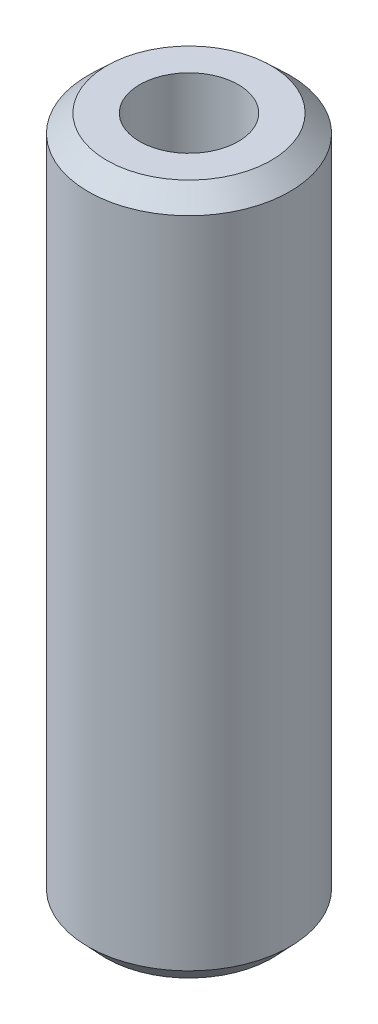
SolidWorks part; units mm, degrees
ref_plane "Front Plane" through (0, 0, 0) normal (0, 0, 1) x (1, 0, 0)
ref_plane "Top Plane" through (0, 0, 0) normal (0, 1, 0) x (1, 0, 0)
ref_plane "Right Plane" through (0, 0, 0) normal (1, 0, 0) x (0, 0, -1)
sketch "Sketch1" plane through (0, 0, 0) normal (0, 1, 0) x (1, 0, 0)
  circle A0 centre (0, 0) radius 15
  dimension "SHAFT_OD" = 30
extrude "Boss-Extrude1" add sketch "Sketch1" along normal blind 102.7057
sketch "Sketch2" plane through (0, 0, 0) normal (0, 1, 0) x (1, 0, 0)
  circle A0 centre (0, 0) radius 7.3371
  dimension "BORE_D" = 14.6743
extrude "Cut-Extrude1" cut sketch "Sketch2" along normal through all
chamfer "Chamfer1" distance 2.629 angle 46.615 2 edges at (0, 102.7057, 15) (0, 0, 15) first distance on face at (0, 102.7057, 15) first distance on face at (0, 0, 7.3371)
